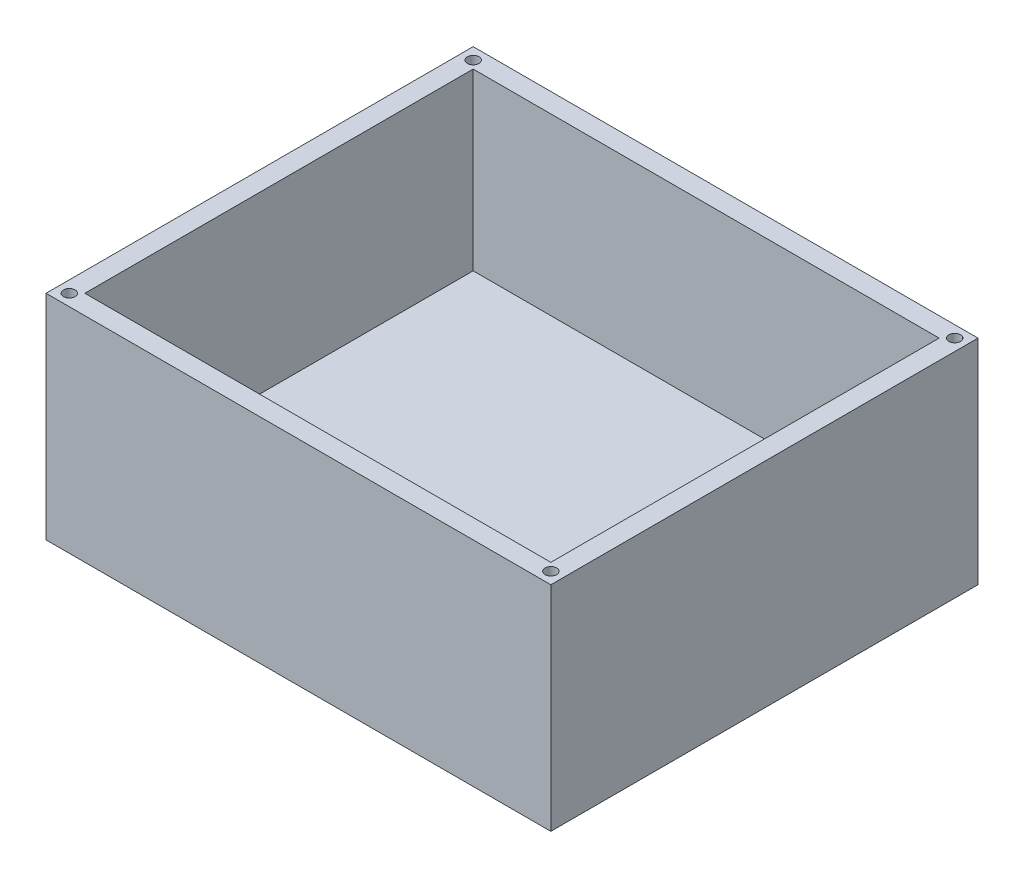
SolidWorks part; units mm, degrees
ref_plane "Front Plane" through (0, 0, 0) normal (0, 0, 1) x (1, 0, 0)
ref_plane "Top Plane" through (0, 0, 0) normal (0, 1, 0) x (1, 0, 0)
ref_plane "Right Plane" through (0, 0, 0) normal (1, 0, 0) x (0, 0, -1)
sketch "Sketch1" plane through (0, 0, 0) normal (0, 1, 0) x (1, 0, 0)
  line L1 (-65, 55) -> (65, 55)
  line L2 (-65, 55) -> (-65, -55)
  line L3 (-65, -55) -> (65, -55)
  line L4 (65, 55) -> (65, -55)
  line L5 (-65, 55) -> (65, -55) construction
  line L6 (-65, -55) -> (65, 55) construction
  point P0 (0, 0)
  dimension "D1" = 130
  dimension "D2" = 110
extrude "Boss-Extrude1" add sketch "Sketch1" along normal blind 10
sketch "Sketch2" plane through (0, 10, 0) normal (0, 1, 0) x (1, 0, 0)
  line L0 (-65, 55) -> (-65, -55) construction
  line L1 (-65, 55) -> (65, 55)
  line L2 (-65, 55) -> (-65, -55)
  line L3 (-65, -55) -> (65, -55)
  line L4 (65, 55) -> (65, -55)
  line L5 (-65, 55) -> (65, -55) construction
  line L6 (-65, -55) -> (65, 55) construction
  line L7 (-60, 50) -> (60, 50)
  line L8 (-60, 50) -> (-60, -50)
  line L9 (-60, -50) -> (60, -50)
  line L10 (60, 50) -> (60, -50)
  line L11 (-60, 50) -> (60, -50) construction
  line L12 (-60, -50) -> (60, 50) construction
  line L13 (-65, -55) -> (65, -55) construction
  point P0 (0, 0)
  point P6 (0, 0)
  dimension "D1" = 5
  dimension "D2" = 5
extrude "Boss-Extrude2" add sketch "Sketch2" along normal blind 45
sketch "Sketch3" plane through (0, 55, 0) normal (0, 1, 0) x (1, 0, 0)
  line L0 (65, 55) -> (-65, 55) construction
  line L1 (-65, 55) -> (-65, -55) construction
  circle A0 centre (-62, 52) radius 1.5
  dimension "D3" = 3
  dimension "D1" = 3
  dimension "D2" = 3
extrude "Cut-Extrude3" cut sketch "Sketch3" against normal blind 20
mirror "Mirror1" about plane through (0, 0, 0) normal (0, 0, 1) of "Cut-Extrude3"
mirror "Mirror2" about plane through (0, 0, 0) normal (1, 0, 0) of "Mirror1"
